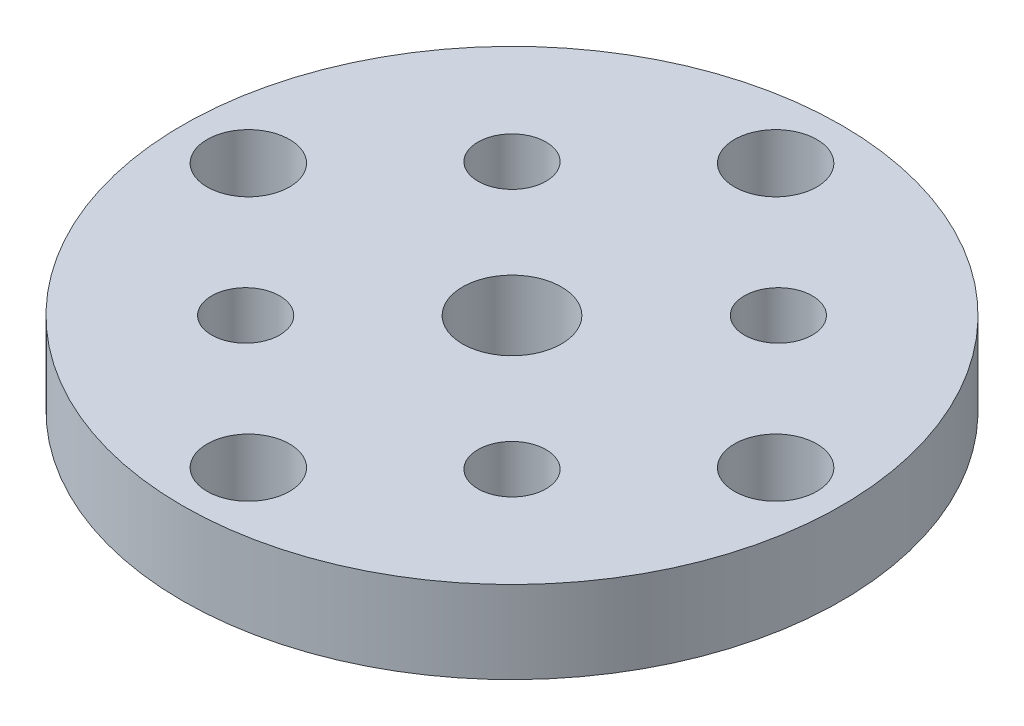
SolidWorks part; units mm, degrees
material "2014-T6"
ref_plane "Front Plane" through (0, 0, 0) normal (0, 0, 1) x (1, 0, 0)
ref_plane "Top Plane" through (0, 0, 0) normal (0, 1, 0) x (1, 0, 0)
ref_plane "Right Plane" through (0, 0, 0) normal (1, 0, 0) x (0, 0, -1)
sketch "Sketch1" plane through (0, 0, 0) normal (0, 1, 0) x (1, 0, 0)
  line L0 (0, 24.1217) -> (0, -25.5168) construction
  line L1 (-33.1168, 0) -> (38.4772, 0) construction
  circle A0 centre (0, 0) radius 10
  circle A1 centre (0, 0) radius 1.5
  circle A2 centre (0, 8) radius 1.25
  circle A3 centre (0, 0) radius 10
  circle A4 centre (8, 0) radius 1.25
  circle A5 centre (0, 0) radius 10
  circle A6 centre (0, -8) radius 1.25
  circle A7 centre (0, 0) radius 10
  circle A8 centre (-8, 0) radius 1.25
  point P22 (0, 0)
  dimension "D1" = 20
  dimension "D2" = 3
  dimension "D3" = 2.5
  dimension "D5" = 8
  dimension "D4" = 4
extrude "Boss-Extrude1" add sketch "Sketch1" along normal blind 2.5 contours A0 A8 A6 A4 A2 A1 region at (-9.7172, 0, 0)
cosmetic thread "Cosmetic Thread1" parameters "D1"=2.4999, "D2"=3
cosmetic thread "Cosmetic Thread2" parameters "D1"=2.4999, "D2"=3
cosmetic thread "Cosmetic Thread3" parameters "D1"=2.4999, "D2"=3
cosmetic thread "Cosmetic Thread4" parameters "D1"=2.4999, "D2"=3
sketch "Sketch2" plane through (0, 2.5, 0) normal (0, 1, 0) x (1, 0, 0)
  line L0 (-10.1496, 10.1496) -> (11.2798, -11.2798) construction
  line L1 (10.8654, 10.8654) -> (-10.8654, -10.8654) construction
  line L2 (0, 10.6288) -> (0, -11.3901) construction
  circle A0 centre (0, 0) radius 5.715 construction
  circle A1 centre (-4.0411, 4.0411) radius 1.0325
  circle A2 centre (4.0411, 4.0411) radius 1.0325
  circle A3 centre (4.0411, -4.0411) radius 1.0325
  circle A4 centre (-4.0411, -4.0411) radius 1.0325
  dimension "D1" = 11.43
  dimension "D3" = 2.065
  dimension "D2" = 45
extrude "Cut-Extrude1" cut sketch "Sketch2" against normal through all
